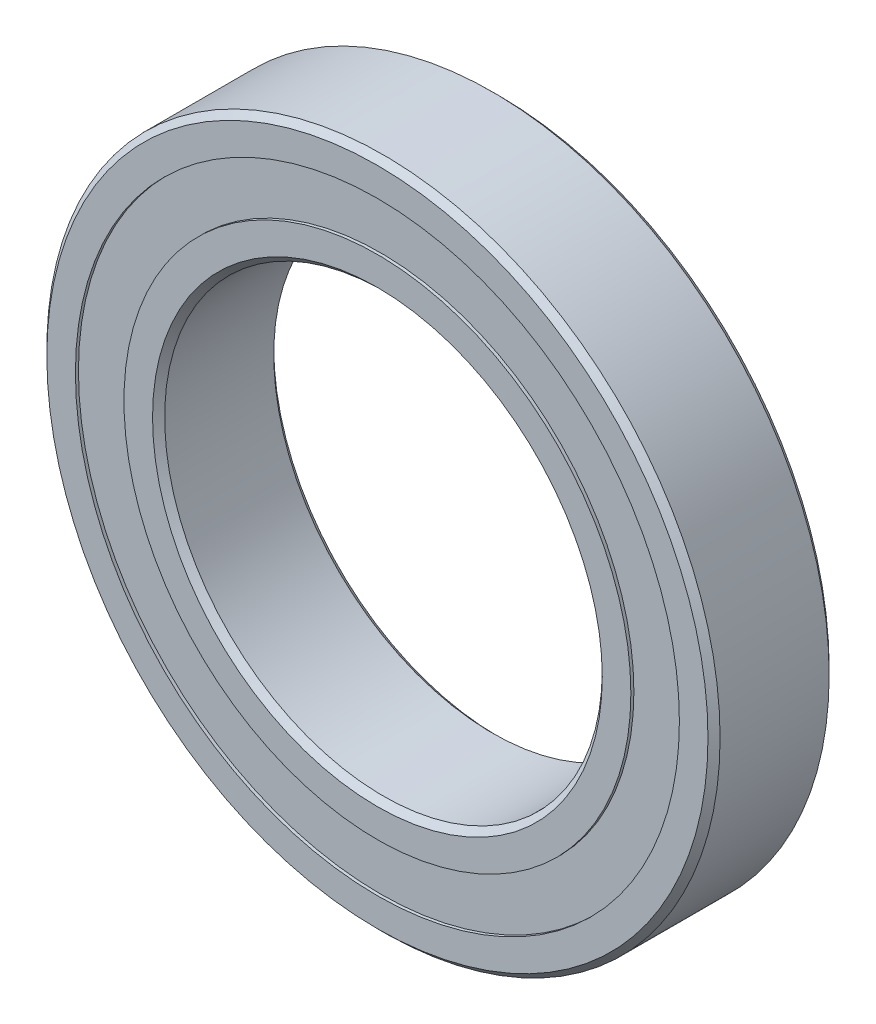
SolidWorks part; units mm, degrees
ref_plane "Front Plane" through (0, 0, 0) normal (0, 0, 1) x (1, 0, 0)
ref_plane "Top Plane" through (0, 0, 0) normal (0, 1, 0) x (1, 0, 0)
ref_plane "Right Plane" through (0, 0, 0) normal (1, 0, 0) x (0, 0, -1)
sketch "Sketch1" plane through (0, 0, 0) normal (1, 0, 0) x (0, 0, -1)
  line L0 (-9, 0) -> (9, 0) construction
  line L1 (0, 50) -> (0, -50) construction
  line L2 (8.1, 50) -> (-8.1, 50)
  line L3 (-8.1, 50) -> (-9, 49.1)
  line L4 (-9, 49.1) -> (-9, 44.8544)
  line L5 (-9, 44.8544) -> (-4, 44.8544)
  line L6 (9, 44.8544) -> (4, 44.8544)
  line L7 (9, 49.1) -> (9, 44.8544)
  line L8 (8.1, 50) -> (9, 49.1)
  line L9 (0, 50) -> (0, 41.25) construction
  line L10 (0, 41.25) -> (0, 32.5) construction
  arc A0 (-4, 44.8544) -> (4, 44.8544) centre (0, 41.25) cw
  point P14 (0, 32.5)
  dimension "Width" = 18
  dimension "OD" = 100
  dimension "D1" = 45
  dimension "D2" = 0.9
  dimension "Shaft Dia" = 65
  dimension "D3" = 8
  dimension "D4" = 3.6044
revolve "Revolve1" add sketch "Sketch1" angle 360 about L0
sketch "Sketch3" plane through (0, 0, 0) normal (1, 0, 0) x (0, 0, -1)
  line L0 (-9, 37.6456) -> (-4, 37.6456)
  line L1 (0, 50) -> (0, -50) construction
  line L2 (-9, 49.1) -> (-9, 44.8544) construction
  line L3 (-9, 37.6456) -> (-9, 33.4)
  line L4 (-8.1, 50) -> (-9, 49.1) construction
  line L5 (-9, 33.4) -> (-8.1, 32.5)
  line L6 (-8.1, 32.5) -> (8.1, 32.5)
  line L7 (8.1, 50) -> (8.1, -50) construction
  line L8 (8.1, 32.5) -> (9, 33.4)
  line L9 (9, -49.1) -> (9, 49.1) construction
  line L10 (9, 33.4) -> (9, 37.6456)
  line L11 (9, 37.6456) -> (4, 37.6456)
  line L13 (8.1, 50) -> (9, 49.1) construction
  arc A0 (4, 44.8544) -> (-4, 44.8544) centre (0, 41.25) ccw construction
  arc A1 (4, 37.6456) -> (-4, 37.6456) centre (0, 41.25) cw
revolve "Revolve3" add sketch "Sketch3" angle 360 about L0
sketch "Sketch4" plane through (0, 0, 0) normal (1, 0, 0) x (0, 0, -1)
  line L0 (-5.3844, 41.25) -> (5.3844, 41.25)
  arc A2 (-5.3844, 41.25) -> (5.3844, 41.25) centre (0, 41.25) cw
  arc A3 (4, 44.8544) -> (-4, 44.8544) centre (0, 41.25) ccw construction
revolve "Revolve4" add sketch "Sketch4" angle 360 about L0
ref_axis "Axis1" through (0, 0, -9) along (0, 0, 1)
pattern_circular "CirPattern1" count 12 every 30 about axis through (0, 0, -9) along (0, 0, 1) of bodies 104
sketch "Sketch5" plane through (0, 0, 0) normal (1, 0, 0) x (0, 0, -1)
  line L0 (-9, 44.8544) -> (-4, 44.8544) construction
  line L1 (-8.55, 44.8544) -> (-5.3844, 44.8544)
  line L2 (-8.55, 44.8544) -> (-8.55, 37.6456)
  line L3 (-8.55, 37.6456) -> (-5.3844, 37.6456)
  line L4 (-5.3844, 44.8544) -> (-5.3844, 37.6456)
  line L5 (-9, 37.6456) -> (-4, 37.6456) construction
  line L6 (9, 44.8544) -> (4, 44.8544) construction
  line L7 (8.55, 44.8544) -> (5.3844, 44.8544)
  line L8 (8.55, 44.8544) -> (8.55, 37.6456)
  line L9 (8.55, 37.6456) -> (5.3844, 37.6456)
  line L10 (5.3844, 44.8544) -> (5.3844, 37.6456)
  line L11 (9, 37.6456) -> (4, 37.6456) construction
  line L12 (-8.1, 50) -> (-9, 49.1) construction
  point P18 (-8.55, 49.55)
revolve "Revolve5" add sketch "Sketch5" angle 360 about L0
equation "\"D2@Sketch1\" = \"Width@Sketch1\"*.05"
equation "\"D3@Sketch1\" = \"Width@Sketch1\"/2.25"
equation "\"D4@Sketch1\" = (((\"OD@Sketch1\"-\"Width@Sketch1\")/2)/3.25)/3.5"
equation "\"D2@CirPattern1\" = 360/\"Balls@CirPattern1\""
